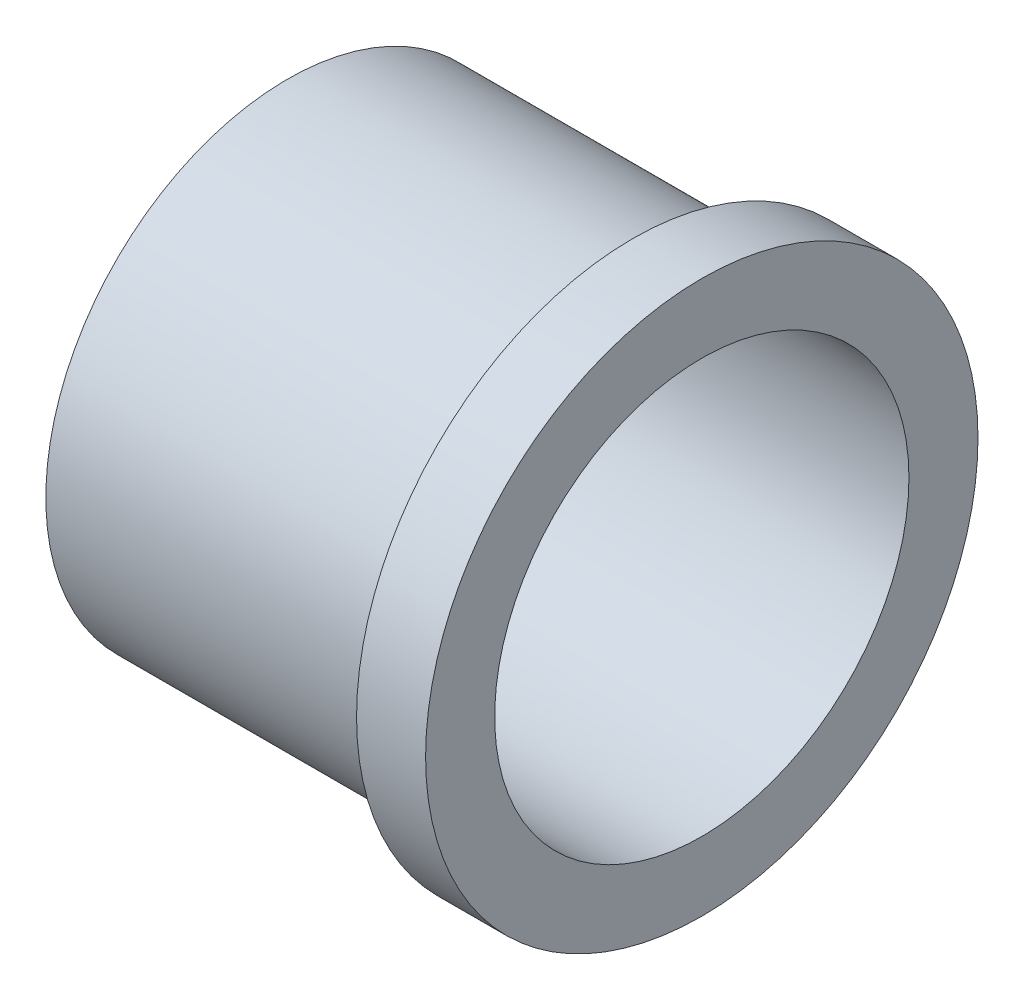
SolidWorks part; units mm, degrees
ref_plane "Alzado" through (0, 0, 0) normal (1, 0, 0) x (0, 1, 0)
ref_plane "Planta" through (0, 0, 0) normal (0, 0, 1) x (0, 1, 0)
ref_plane "Vista lateral" through (0, 0, 0) normal (0, 1, 0) x (-1, 0, 0)
sketch "Croquis1" plane through (0, 0, 0) normal (0, 1, 0) x (-1, 0, 0)
  line L0 (0, 4) -> (0, 3)
  line L1 (0, 3) -> (6, 3)
  line L2 (6, 3) -> (6, 3.5)
  line L3 (6, 3.5) -> (1, 3.5)
  line L4 (1, 3.5) -> (1, 4)
  line L5 (1, 4) -> (0, 4)
  line L6 (0, 0) -> (6, 0) construction
  point P9 (0, 3.5)
  dimension "D1" = 6
  dimension "D2" = 1
  dimension "D3" = 1
  dimension "D4" = 6
revolve "Revolución1" add sketch "Croquis1" angle 360 about L6
